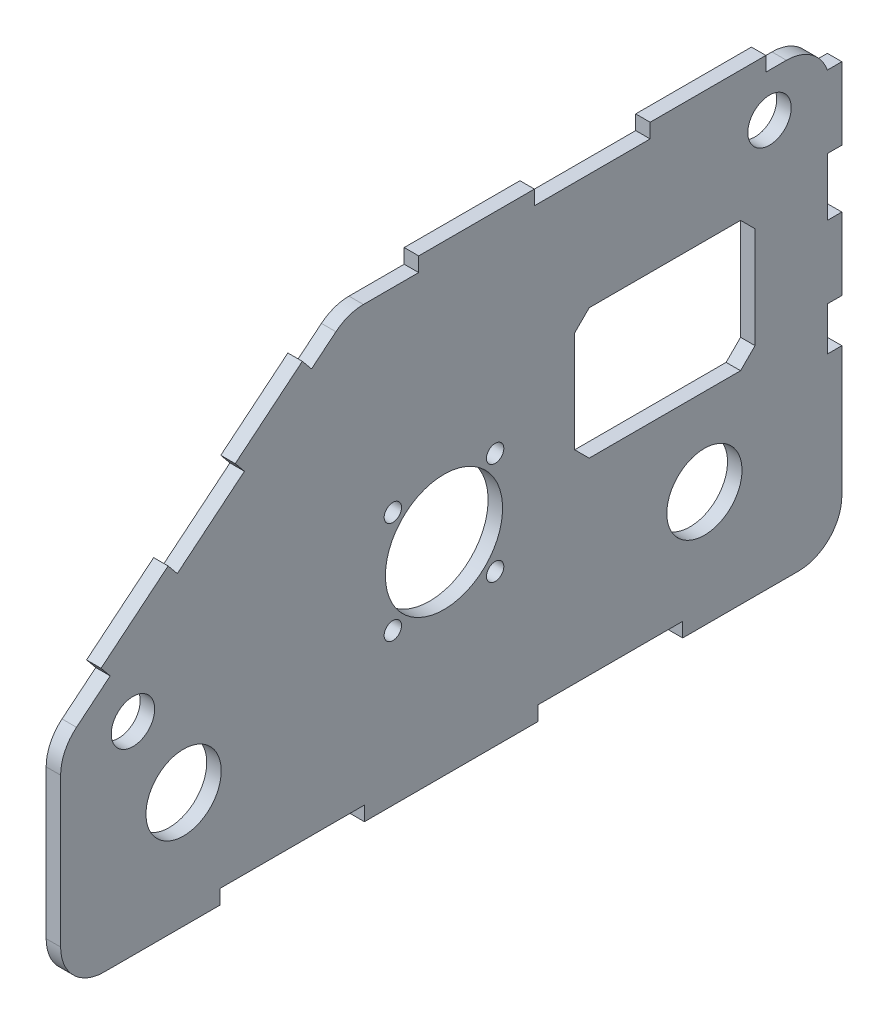
SolidWorks part; units mm, degrees
ref_plane "Plan de face" through (0, 0, 0) normal (0, 0, 1) x (1, 0, 0)
ref_plane "Plan de dessus" through (0, 0, 0) normal (0, 1, 0) x (1, 0, 0)
ref_plane "Plan de droite" through (0, 0, 0) normal (1, 0, 0) x (0, 0, -1)
sketch "Esquisse1" plane through (0, 0, 0) normal (1, 0, 0) x (0, 0, -1)
  line L0 (0, 0) -> (540, 0) construction
  line L1 (540, 0) -> (540, 310)
  line L2 (540, 310) -> (195, 310)
  line L3 (195, 310) -> (0, 150)
  line L4 (0, 150) -> (0, 0)
  line L5 (0, 150) -> (195, 150) construction
  line L6 (195, 150) -> (195, 310) construction
  line L7 (195, 150) -> (195, 0) construction
  line L8 (490, 0) -> (490, 270) construction
  line L9 (490, 270) -> (540, 270) construction
  line L10 (50, 130) -> (50, 0) construction
  line L11 (50, 0) -> (50, 130) construction
  line L12 (50, 130) -> (0, 130) construction
  line L13 (540, 0) -> (540, -10) construction
  line L14 (540, -10) -> (0, -10) construction
  line L15 (0, -10) -> (0, 0) construction
  line L16 (430, 0) -> (330, 0)
  line L17 (430, 0) -> (430, -10)
  line L18 (210, 0) -> (110, 0)
  line L19 (330, -10) -> (330, 0)
  line L21 (210, 0) -> (210, -10)
  line L23 (110, -10) -> (110, 0)
  line L25 (270, 0) -> (270, -10) construction
  line L26 (540, 0) -> (540, -10)
  line L27 (540, -10) -> (430, -10)
  line L28 (330, -10) -> (210, -10)
  line L29 (0, 0) -> (0, -10)
  line L30 (0, -10) -> (110, -10)
  circle A0 centre (490, 270) radius 15
  circle A1 centre (50, 130) radius 15
  dimension "D1" = 30
  dimension "D2" = 30
  dimension "D3" = 40
  dimension "D4" = 20
  dimension "D5" = 440
  dimension "D6" = 10
  dimension "D7" = 50
  dimension "D8" = 50
  dimension "D9" = 195
  dimension "D10" = 150
  dimension "D11" = 140
  dimension "D12" = 100
  dimension "D13" = 100
  dimension "D14" = 120
extrude "Boss.-Extru.1" add sketch "Esquisse1" along normal blind 10
sketch "Esquisse5" plane through (0, 0, 0) normal (-1, 0, 0) x (0, 0, 1)
  line L0 (-265, 310) -> (-265, -10) construction
  line L1 (-305.5, 130) -> (-224.5, 130) construction
  line L2 (-540, 310) -> (-195, 310) construction
  line L3 (-210, -10) -> (-330, -10) construction
  line L4 (-590, 130) -> (40, 130) construction
  line L5 (-540, -10) -> (-540, 310) construction
  line L7 (-430, -10) -> (-540, -10) construction
  line L10 (-265, 130) -> (-265, 80.0076) construction
  line L12 (-265, 130) -> (-300.35, 94.65) construction
  circle A0 centre (-265, 130) radius 40.5
  circle A4 centre (-265, 130) radius 49.9924 construction
  circle A5 centre (-300.35, 94.65) radius 6
  circle A6 centre (-300.35, 165.35) radius 6
  circle A7 centre (-229.65, 165.35) radius 6
  circle A8 centre (-229.65, 94.65) radius 6
  point P31 (-265, 130)
  dimension "D1" = 70.7
  dimension "D2" = 81
  dimension "D6" = 12
  dimension "D3" = 275
  dimension "D4" = 140
  dimension "D8" = 45
  dimension "D7" = 4
extrude "Enlèv. mat.-Extru.1" cut sketch "Esquisse5" against normal blind 10
sketch "Esquisse6" plane through (0, 0, 0) normal (-1, 0, 0) x (0, 0, 1)
  line L0 (-445, 70) -> (-265, 70) construction
  line L1 (-265, 130) -> (-265, 70) construction
  circle A0 centre (-445, 70) radius 26
  circle A1 centre (-85, 70) radius 26
  dimension "D2" = 52
  dimension "D1" = 180
  dimension "D3" = 60
extrude "Enlèv. mat.-Extru.2" cut sketch "Esquisse6" against normal blind 10
sketch "Esquisse7" plane through (0, 0, 0) normal (-1, 0, 0) x (0, 0, 1)
  line L0 (-540, 300) -> (-198.5775, 300) construction
  line L1 (-540, -10) -> (-540, 310) construction
  line L2 (0, 137.0646) -> (-198.5775, 300) construction
  line L3 (0, 150) -> (0, -10) construction
  line L4 (-195, 310) -> (0, 150) construction
  line L5 (-540, 310) -> (-195, 310) construction
  line L6 (-198.5775, 300) -> (-247.5, 300)
  line L7 (-247.5, 300) -> (-247.5, 310)
  line L8 (-247.5, 310) -> (-327.5, 310)
  line L9 (-327.5, 310) -> (-327.5, 300)
  line L10 (-327.5, 300) -> (-407.5, 300)
  line L11 (-367.5, 300) -> (-367.5, 310) construction
  line L12 (-487.5, 300) -> (-487.5, 310)
  line L13 (-487.5, 310) -> (-407.5, 310)
  line L14 (-407.5, 310) -> (-407.5, 300)
  line L15 (-530, 310) -> (-530, -10) construction
  line L16 (-540, 310) -> (-195, 310) construction
  line L17 (-430, -10) -> (-540, -10) construction
  line L18 (-540, -10) -> (-540, 310) construction
  line L19 (-487.5, 300) -> (-530, 300)
  line L20 (-530, 300) -> (-530, 280)
  line L21 (-530, 280) -> (-540, 280)
  line L22 (-540, 280) -> (-540, 230)
  line L23 (-540, 230) -> (-530, 230)
  line L24 (-530, 230) -> (-530, 190)
  line L25 (-530, 190) -> (-540, 190)
  line L26 (-540, 190) -> (-540, 140)
  line L27 (-540, 140) -> (-530, 140)
  line L28 (-530, 140) -> (-530, 110)
  line L29 (-530, 110) -> (-794.7805, 110)
  line L30 (-794.7805, 110) -> (-794.7805, 495.7328)
  line L31 (-794.7805, 495.7328) -> (95.6318, 495.7328)
  line L32 (95.6318, 495.7328) -> (95.6318, 137.0646)
  line L33 (95.6318, 137.0646) -> (0, 137.0646)
  line L34 (0, 137.0646) -> (-34.2666, 165.1808)
  line L35 (-34.2666, 165.1808) -> (-27.9234, 172.9115)
  line L36 (-195, 310) -> (0, 150) construction
  line L37 (-27.9234, 172.9115) -> (-74.3078, 210.9705)
  line L38 (-74.3078, 210.9705) -> (-80.651, 203.2398)
  line L39 (-80.651, 203.2398) -> (-127.0354, 241.2988)
  line L40 (-103.8432, 222.2693) -> (-97.5, 230) construction
  line L41 (-120.6922, 249.0295) -> (-127.0354, 241.2988)
  line L42 (-167.0766, 287.0885) -> (-120.6922, 249.0295)
  line L43 (-173.4198, 279.3578) -> (-167.0766, 287.0885)
  line L44 (-198.5775, 300) -> (-173.4198, 279.3578)
  dimension "D1" = 10
  dimension "D2" = 10
  dimension "D3" = 40
  dimension "D4" = 80
  dimension "D5" = 10
  dimension "D6" = 30
  dimension "D7" = 60
  dimension "D8" = 50
  dimension "D9" = 50
  dimension "D10" = 40
  dimension "D11" = 30
  dimension "D12" = 30
extrude "Enlèv. mat.-Extru.3" cut sketch "Esquisse7" against normal blind 10
fillet "Congé1" radius 30 5 edges at (5, -10, -540) (5, 300, -530) (5, -10, 0) (5, 137.0646, 0) (5, 300, -198.5775)
sketch "Esquisse8" plane through (0, 0, 0) normal (-1, 0, 0) x (0, 0, 1)
  line L0 (-355.35, 210) -> (-365.35, 220)
  line L1 (-365.35, 220) -> (-470, 220)
  line L2 (-355.35, 210) -> (-355.35, 140)
  line L3 (-365.35, 130) -> (-470, 130)
  line L4 (-480, 210) -> (-480, 140)
  line L5 (-355.35, 140) -> (-365.35, 130)
  line L6 (-470, 130) -> (-480, 140)
  line L7 (-470, 220) -> (-480, 210)
  line L14 (-530, 190) -> (-530, 230) construction
  line L15 (-407.5, 300) -> (-327.5, 300) construction
  line L16 (-300.35, 165.35) -> (-300.35, 94.65) construction
  point P0 (-355.35, 220)
  point P1 (-480, 130)
  point P2 (-355.35, 130)
  point P3 (-480, 220)
  point P14 (-480, 175)
  point P27 (-300.35, 165.35)
  point P28 (-300.35, 94.65)
  dimension "D1" = 50
  dimension "D2" = 80
  dimension "D7" = 90
  dimension "55" = 55
extrude "Enlèv. mat.-Extru.4" cut sketch "Esquisse8" against normal blind 10
